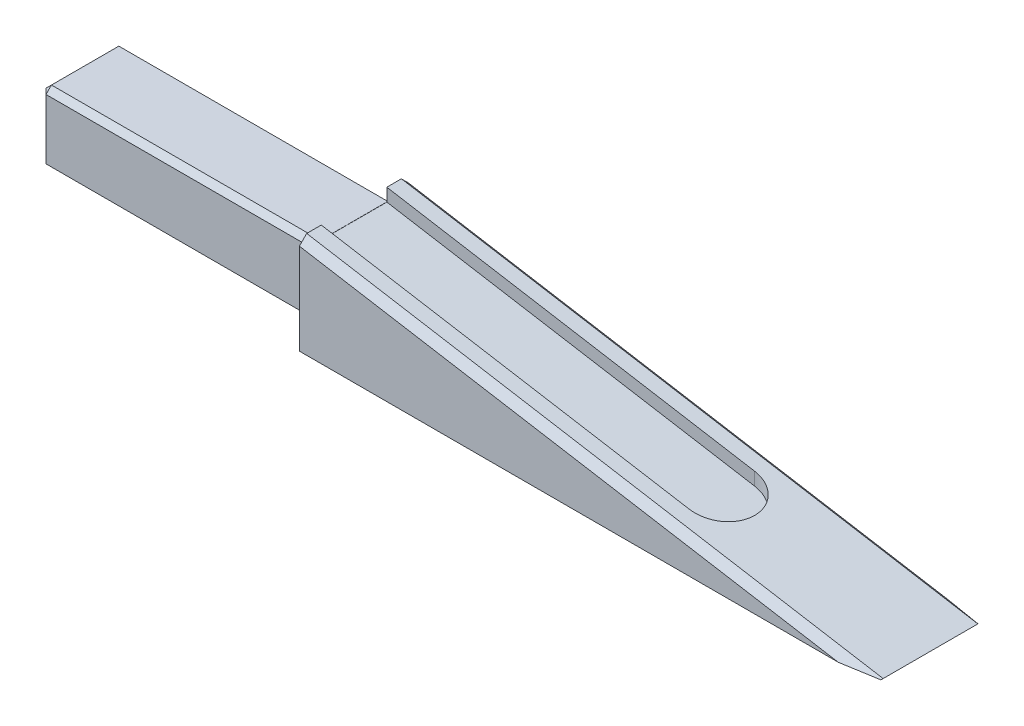
SolidWorks part; units mm, degrees
ref_plane "Front Plane" through (0, 0, 0) normal (0, 0, 1) x (1, 0, 0)
ref_plane "Top Plane" through (0, 0, 0) normal (0, 1, 0) x (1, 0, 0)
ref_plane "Right Plane" through (0, 0, 0) normal (1, 0, 0) x (0, 0, -1)
sketch "Sketch2" plane through (0, 0, 0) normal (0, 0, 1) x (1, 0, 0)
  line L0 (0, 0) -> (80, 0)
  line L5 (0, 0) -> (0, 13.5)
  line L6 (0, 13.5) -> (80, 0)
  dimension "D1" = 80
  dimension "D2" = 13.5
extrude "Boss-Extrude1" add sketch "Sketch2" along normal mid plane 15
sketch "Sketch3" plane through (0, 0, 0) normal (-1, 0, 0) x (0, 0, 1)
  line L0 (7.5, 0) -> (-7.5, 0) construction
  line L1 (-5.375, 2) -> (5.375, 2)
  line L2 (-5.375, 2) -> (-5.375, 11.75)
  line L3 (-5.375, 11.75) -> (5.375, 11.75)
  line L4 (5.375, 2) -> (5.375, 11.75)
  point P6 (0, 2)
  dimension "D1" = 9.75
  dimension "D2" = 10.75
  dimension "D3" = 2
extrude "Boss-Extrude2" add sketch "Sketch3" along normal blind 37.67
sketch "Sketch4" plane through (0, 0, 7.5) normal (0, 0, 1) x (1, 0, 0)
  line L0 (0, 13.5) -> (80, 0)
  line L1 (0, 11.7253) -> (55, 2.444)
  line L2 (0, 13.5) -> (0, 11.7253)
  line L3 (0, 2) -> (0, 11.75) construction
  line L4 (55, 4.2188) -> (55, 2.444)
  line L5 (0, 13.5) -> (55, 4.2188)
  line L8 (-0.2912, 11.7744) -> (79.7088, -1.7256) construction
  line L9 (0, 13.5) -> (0, 0) construction
  line M3 (0, 13.5) -> (0, 0)
  dimension "D1" = 1.75
  dimension "D2" = 25
extrude "Cut-Extrude9" cut sketch "Sketch4" against normal blind 9 from offset 3 contours L4 L0 L1 M3 offset against normal yes
fillet "Fillet1" radius 4.5 4 edges at (55, 3.3314, 4.5) (55, 4.2188, 0) (55, 2.444, 0) (55, 3.3314, -4.5)
chamfer "Chamfer1" distance 1 angle 45 3 edges at (80, 0, 0) (40, 6.75, -7.5) (40, 6.75, 7.5)
chamfer "Chamfer3" distance 0.75 angle 45 8 edges at (-37.67, 2, 0) (-18.835, 2, -5.375) (-18.835, 2, 5.375) (-37.67, 6.875, 5.375) (-18.835, 11.75, 5.375) (-37.67, 11.75, 0) (-37.67, 6.875, -5.375) (-18.835, 11.75, -5.375)
